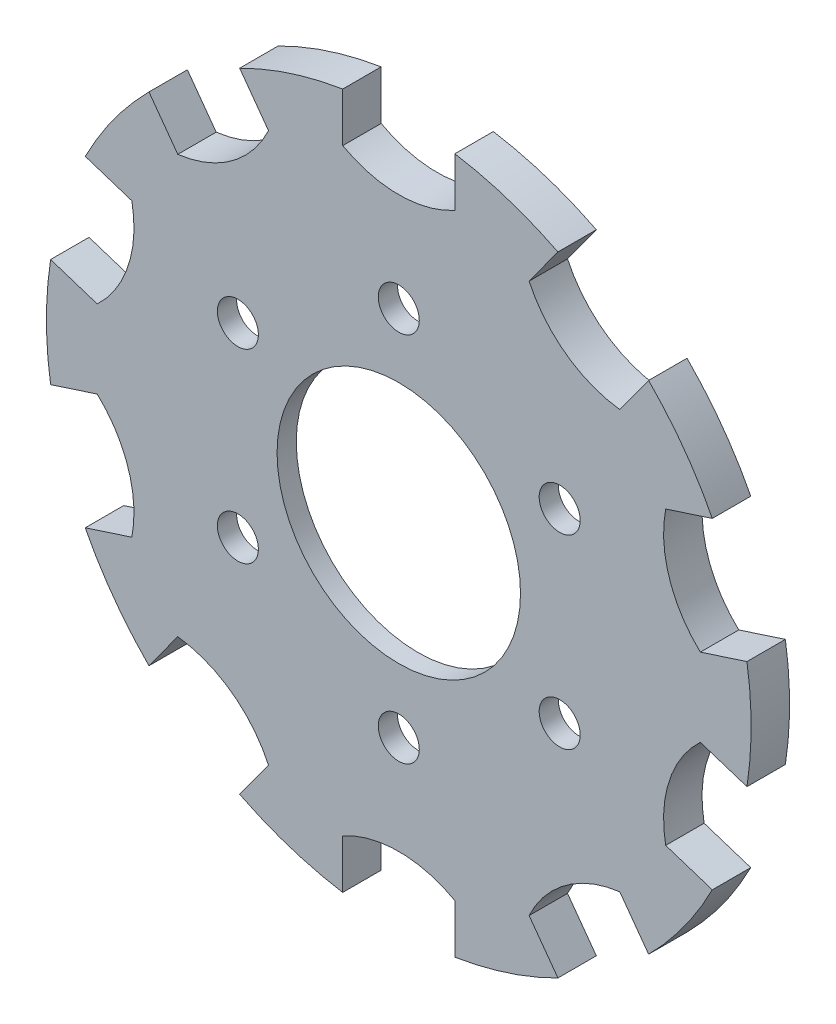
SolidWorks part; units mm, degrees
ref_plane "Front Plane" through (0, 0, 0) normal (0, 0, 1) x (1, 0, 0)
ref_plane "Top Plane" through (0, 0, 0) normal (0, 1, 0) x (1, 0, 0)
ref_plane "Right Plane" through (0, 0, 0) normal (1, 0, 0) x (0, 0, -1)
sketch "Sketch2" plane through (0, 0, 0) normal (0, 0, 1) x (1, 0, 0)
  line L2 (-4.375, 27.1498) -> (-4.375, 23.324)
  line L3 (4.375, 27.1498) -> (4.375, 23.324)
  line L4 (19.4977, 19.3931) -> (17.249, 16.298)
  line L5 (12.4188, 24.5362) -> (10.1701, 21.4411)
  line L6 (27.1729, 4.2289) -> (23.5344, 3.0466)
  line L7 (24.469, 12.5506) -> (20.8305, 11.3684)
  line L8 (24.469, -12.5506) -> (20.8305, -11.3684)
  line L9 (27.1729, -4.2289) -> (23.5344, -3.0466)
  line L10 (12.4188, -24.5362) -> (10.1701, -21.4411)
  line L11 (19.4977, -19.3931) -> (17.249, -16.298)
  line L12 (-4.375, -27.1498) -> (-4.375, -23.324)
  line L13 (4.375, -27.1498) -> (4.375, -23.324)
  line L14 (-19.4977, -19.3931) -> (-17.249, -16.298)
  line L15 (-12.4188, -24.5362) -> (-10.1701, -21.4411)
  line L16 (-27.1729, -4.2289) -> (-23.5344, -3.0466)
  line L17 (-24.469, -12.5506) -> (-20.8305, -11.3684)
  line L18 (-24.469, 12.5506) -> (-20.8305, 11.3684)
  line L19 (-27.1729, 4.2289) -> (-23.5344, 3.0466)
  line L20 (-12.4188, 24.5362) -> (-10.1701, 21.4411)
  line L21 (-19.4977, 19.3931) -> (-17.249, 16.298)
  circle A0 centre (0, 0) radius 27.5
  circle A1 centre (0, 0) radius 14.5 construction
  circle A2 centre (0, 0) radius 18.75 construction
  circle A3 centre (-12.5574, 7.25) radius 1.6
  circle A4 centre (0, 14.5) radius 1.6
  circle A5 centre (12.5574, 7.25) radius 1.6
  circle A6 centre (12.5574, -7.25) radius 1.6
  circle A7 centre (0, -14.5) radius 1.6
  circle A8 centre (-12.5574, -7.25) radius 1.6
  arc A9 (-4.375, 23.324) -> (4.375, 23.324) centre (0, 31.2162) ccw
  arc A10 (10.1701, 21.4411) -> (17.249, 16.298) centre (18.3484, 25.2544) ccw
  arc A11 (20.8305, 11.3684) -> (23.5344, 3.0466) centre (29.6883, 9.6463) ccw
  arc A12 (23.5344, -3.0466) -> (20.8305, -11.3684) centre (29.6883, -9.6463) ccw
  arc A13 (17.249, -16.298) -> (10.1701, -21.4411) centre (18.3484, -25.2544) ccw
  arc A14 (4.375, -23.324) -> (-4.375, -23.324) centre (0, -31.2162) ccw
  arc A15 (-10.1701, -21.4411) -> (-17.249, -16.298) centre (-18.3484, -25.2544) ccw
  arc A16 (-20.8305, -11.3684) -> (-23.5344, -3.0466) centre (-29.6883, -9.6463) ccw
  arc A17 (-23.5344, 3.0466) -> (-20.8305, 11.3684) centre (-29.6883, 9.6463) ccw
  arc A18 (-17.249, 16.298) -> (-10.1701, 21.4411) centre (-18.3484, 25.2544) ccw
  circle A19 centre (0, 0) radius 9.5
  circle A20 centre (0, 0) radius 18.75
  point P25 (0, 0)
  point P75 (0, 0)
  dimension "D1" = 55
  dimension "37" = 29
  dimension "D3" = 37.5
  dimension "D4" = 3.2
  dimension "D8" = 19
  dimension "D6" = 10
  dimension "D7" = 8.75
  dimension "D5" = 6
extrude "Boss-Extrude2" add sketch "Sketch2" along normal blind 3 contours A18 L21 A0 L18 A17 L19 L16 A16 L17 L14 A15 L15 L12 A14 L13 L10 A13 L11 L8 A12 L9 L6 A11 L7 L4 A10 L5 L3 A9 L2 L20 A8 A1 A3 A4 A5 A6 | A8 A1 A7 A6 A5 A4 A3 A19 region at (-5.1479, 25.2369, 0) region at (-18.2197, 0, 0)
extrude "Boss-Extrude3" add sketch "Sketch2<4>" along normal blind 3 contours A20 A8 A1 A3 A4 A5 A6 A7 region at (-18.2197, 0, 0)
sketch "Sketch2<4>" plane through (0, 0, 0) normal (0, 0, 1) x (1, 0, 0) same geometry as "Sketch2"
extrude "Cut-Extrude2" cut sketch "Sketch2<6>" along normal offset from surface (1.5 mm away) 1.5 contours A20 A8 A1 A3 A4 A5 A6 A7 | A8 A1 A7 A6 A5 A4 A3 A19 region at (-18.2197, 0, 0) up to face at (0, 0, 0)
sketch "Sketch2<6>" plane through (0, 0, 0) normal (0, 0, 1) x (1, 0, 0) same geometry as "Sketch2"
